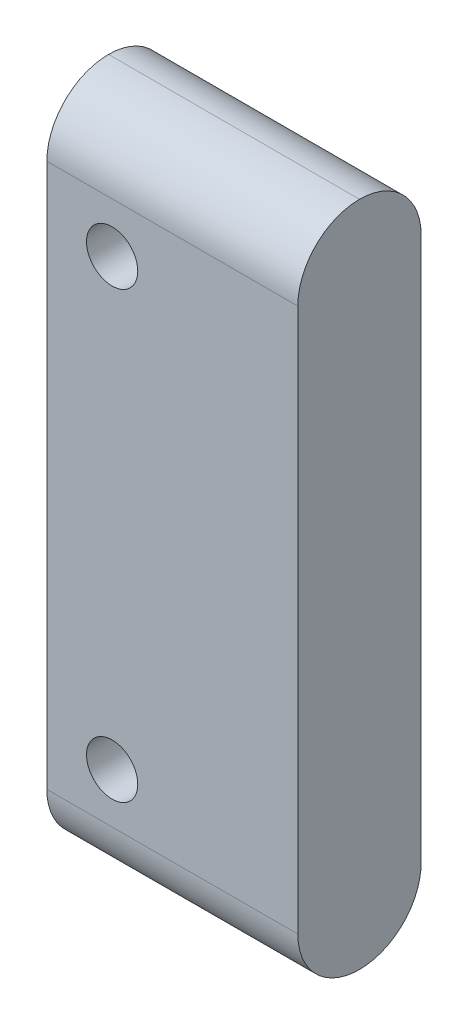
SolidWorks part; units mm, degrees
ref_plane "Front Plane" through (0, 0, 0) normal (0, 0, 1) x (1, 0, 0)
ref_plane "Top Plane" through (0, 0, 0) normal (0, 1, 0) x (1, 0, 0)
ref_plane "Right Plane" through (0, 0, 0) normal (1, 0, 0) x (0, 0, -1)
sketch "Sketch1" plane through (0, 0, 0) normal (0, 0, 1) x (1, 0, 0)
  line L0 (131.1184, 88.3896) -> (98.8184, 88.3592)
  line L1 (98.8184, 174.2592) -> (131.1184, 174.2592)
  line L2 (131.1184, 88.3896) -> (131.1184, 174.2592) construction
  line L3 (98.8184, 88.3592) -> (98.8184, 174.2592)
  line L4 (131.1184, 174.2592) -> (131.1184, 88.3896)
  circle A2 centre (107.2184, 102.7092) radius 3.3
  circle A3 centre (107.2184, 159.9092) radius 3.3
extrude "Extrude1" add sketch "Sketch1" against normal blind 15.875
fillet "Fillet1" radius 7.9375 4 edges at (114.9684, 88.3744, -15.875) (114.9684, 88.3744, 0) (114.9684, 174.2592, -15.875) (114.9684, 174.2592, 0)
